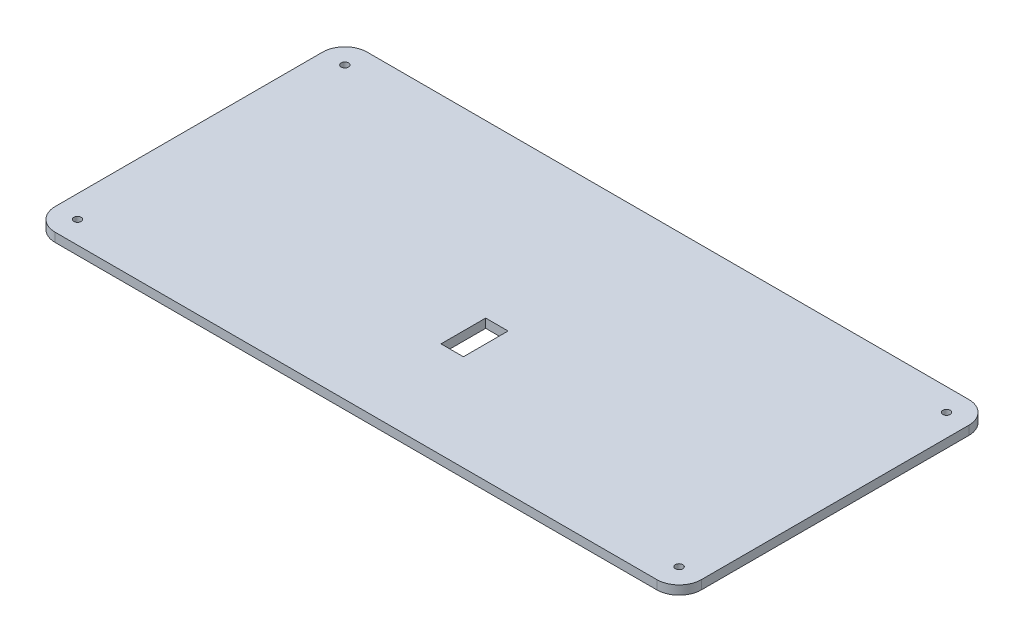
SolidWorks part; units mm, degrees
ref_plane "Front Plane" through (0, 0, 0) normal (0, 0, 1) x (1, 0, 0)
ref_plane "Top Plane" through (0, 0, 0) normal (0, 1, 0) x (1, 0, 0)
ref_plane "Right Plane" through (0, 0, 0) normal (1, 0, 0) x (0, 0, -1)
sketch "Sketch1" plane through (0, 0, 0) normal (0, 1, 0) x (1, 0, 0)
  line L0 (0, 0) -> (145, 0) construction
  line L1 (145, 0) -> (145, -60)
  line L2 (135, -70) -> (0, -70)
  line L3 (0, -70) -> (0, 0)
  line L4 (0, 0) -> (145, 0)
  arc A0 (135, -70) -> (145, -60) centre (135, -60) ccw
  circle A1 centre (135, -60) radius 1.65
  point P7 (145, -70)
  dimension "D4" = 10
  dimension "D5" = 3.3
  dimension "D1" = 145
  dimension "D2" = 70
  dimension "D3" = 145
extrude "Boss-Extrude1" add sketch "Sketch1" along normal blind 4 contours L2 A0 L1 L4 L3 A1 region at (72.2982, 0, 34.9094)
mirror "Mirror1" about plane through (0, 0, 0) normal (1, 0, 0) of "Boss-Extrude1"
mirror "Mirror2" about plane through (0, 0, 0) normal (0, 0, 1) of "Mirror1"
sketch "Sketch2" plane through (0, 4, 0) normal (0, 1, 0) x (1, 0, 0)
  line L0 (-4.55, -26.3091) -> (4.45, -26.3091) construction
  line L1 (4.45, -26.3091) -> (4.5, -7.2591) construction
  line L2 (4.5, -7.2591) -> (-4.5, -7.2591) construction
  line L3 (4.5, -14.3091) -> (4.5, -7.2591) construction
  line L4 (4.5, -7.2591) -> (-4.5, -7.2591) construction
  line L5 (-4.5, -7.2591) -> (-4.55, -26.3091) construction
  line L6 (-4.55, -26.3091) -> (-5.05, -26.3091) construction
  line L7 (-5.05, -26.3091) -> (-5.05, -26.8091) construction
  line L8 (4.5, -7.2591) -> (4.5, -6.7591) construction
  line L9 (4.5, -6.7591) -> (5, -6.7591) construction
  line L11 (-5.05, -26.8091) -> (5, -26.8091)
  line L12 (-5.05, -26.8091) -> (-5.05, -6.7591)
  line L13 (-5.05, -6.7591) -> (5, -6.7591)
  line L14 (5, -26.8091) -> (5, -6.7591)
  dimension "D1" = 0.5
  dimension "D2" = 0.5
  dimension "D3" = 0.5
  dimension "D4" = 0.5
extrude "Cut-Extrude5" cut sketch "Sketch2" against normal through all
